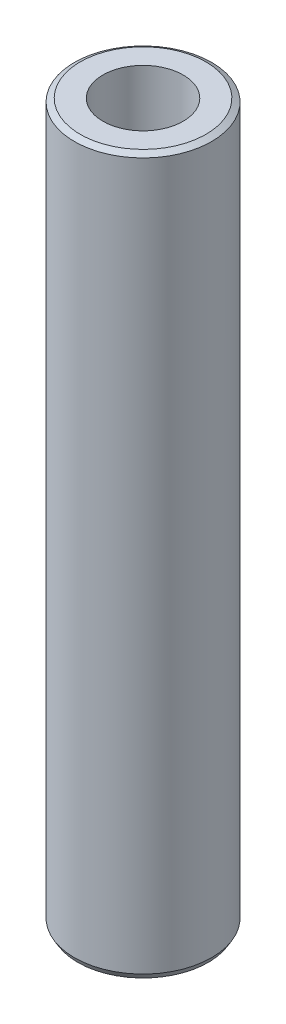
SolidWorks part; units mm, degrees
ref_plane "Front Plane" through (0, 0, 0) normal (0, 0, 1) x (1, 0, 0)
ref_plane "Top Plane" through (0, 0, 0) normal (0, 1, 0) x (1, 0, 0)
ref_plane "Right Plane" through (0, 0, 0) normal (1, 0, 0) x (0, 0, -1)
sketch "Sketch1" plane through (0, 0, 0) normal (0, 1, 0) x (1, 0, 0)
  circle A0 centre (0, 0) radius 57.5
  dimension "SHAFT_OD" = 115
extrude "Boss-Extrude1" add sketch "Sketch1" along normal blind 600
sketch "Sketch2" plane through (0, 0, 0) normal (0, 1, 0) x (1, 0, 0)
  circle A0 centre (0, 0) radius 33.6478
  dimension "BORE_D" = 67.2956
extrude "Cut-Extrude1" cut sketch "Sketch2" along normal through all
chamfer "Chamfer1" distance 2.7922 angle 60 2 edges at (0, 600, 57.5) (0, 0, 57.5) first distance on face at (0, 600, 57.5) first distance on face at (0, 0, 33.6478)
